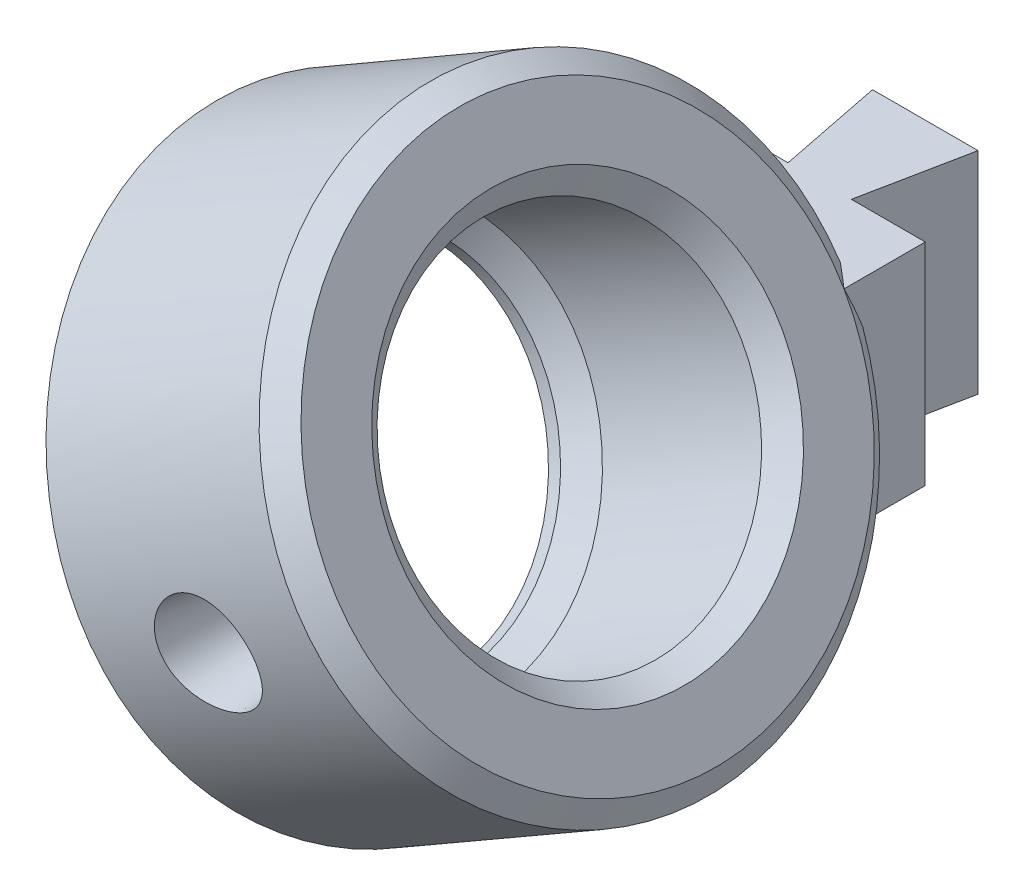
SolidWorks part; units mm, degrees
ref_plane "Front Plane" through (0, 0, 0) normal (0, 0, 1) x (1, 0, 0)
ref_plane "Top Plane" through (0, 0, 0) normal (0, 1, 0) x (1, 0, 0)
ref_plane "Right Plane" through (0, 0, 0) normal (1, 0, 0) x (0, 0, -1)
sketch "Sketch1" plane through (0, 0, 0) normal (0, 1, 0) x (1, 0, 0)
  line L0 (-3.5, 0) -> (-2.5, 5)
  line L1 (-2.5, 5) -> (-7.5, 5)
  line L2 (-7.5, 5) -> (-6.5, 0)
  line L3 (-6.5, 0) -> (-10, 0)
  line L4 (-10, 0) -> (-10, -2.85)
  line L5 (-10, -2.85) -> (0, -2.85)
  line L6 (0, -2.85) -> (0, 0)
  line L7 (0, 0) -> (-3.5, 0)
  line L8 (-5, 5) -> (-5, -2.85)
  dimension "D1" = 5
  dimension "D2" = 5
  dimension "D3" = 3
  dimension "D4" = 1.5
  dimension "D5" = 10
  dimension "D6" = 2.85
extrude "Boss-Extrude1" add sketch "Sketch1" along normal blind 10 contours L8 L1 L2 L3 L4 L5 | L1 L8 L5 L6 L7 L0 region at (-1.75, 0, 0.0931) region at (-5.0931, 0, -1.075)
sketch3d "3DSketch1" plane through (0, 0, 0) normal (0, 0, 1) x (1, 0, 0)
  dimension "D1" = 120
sketch "Sketch2" plane through (4.3301, 2.5, 0) normal (-0.866, -0.5, 0) x (0, 0, -1)
  line L6 (-2.85, -13.6603) -> (-2.85, -5) construction
  line L7 (-2.85, -8.6603) -> (0, -8.6603) construction
  circle A0 centre (-16, -8.6603) radius 13.15
  circle A1 centre (-16, -8.6603) radius 8.15
  dimension "D1" = 16.3
  dimension "D2" = 5
extrude "Boss-Extrude2" add sketch "Sketch2" along normal up to vertex (13.6603 mm away) separate body up to point (-10, 0, 2.85)
sketch "Sketch3" plane through (0, 0, 2.85) normal (0, 0, 1) x (1, 0, 0)
  line L4 (-10, 0) -> (0, 0)
  line L5 (0, 0) -> (0, 10)
  line L6 (0, 10) -> (-10, 10)
  line L7 (-10, 10) -> (-10, 0)
  line L8 (-10, 0) -> (0, 0)
  line L9 (0, 0) -> (0, 10)
  line L10 (0, 10) -> (-10, 10)
  line L11 (-10, 10) -> (-10, 0)
  dimension "D1" = 0
extrude "Boss-Extrude4" add sketch "Sketch3" along normal up to surface up to face at (-5.2551, -8.2184, 16)
sketch "Sketch4" plane through (4.3301, 2.5, 0) normal (0.866, 0.5, 0) x (0, 0, -1)
  circle A0 centre (-16, 8.6603) radius 9.15
  circle A1 centre (-16, 8.6603) radius 8.15 construction
  dimension "D1" = 1
extrude "Cut-Extrude1" cut sketch "Sketch4" against normal blind 9 from offset 2 offset against normal yes
chamfer "Chamfer3" distance 1 angle 45 2 edges at (-5.8071, 16.0581, 16) (-13.6013, 11.5581, 16)
chamfer "Chamfer4" distance 1 angle 45 4 edges at (-7.7551, -3.8882, 16) (-5.2551, -8.2184, 16) (4.075, 2.9419, 16) (6.575, -1.3882, 16)
sketch "Sketch5" plane through (0, 0, -5) normal (0, 0, -1) x (-1, 0, 0)
  line L0 (2.5, 10) -> (7.5, 10) construction
  line L1 (2.5, 10) -> (2.5, 0) construction
  circle A0 centre (5, 5) radius 2.5
  dimension "D1" = 5
  dimension "D2" = 5
  dimension "D3" = 2.5
extrude "Cut-Extrude2" cut sketch "Sketch5" along normal blind 9 draft 7 from offset 35 offset against normal yes
equation "\"D4@Sketch1\"=\"D3@Sketch1\"/2"
equation "\"D6@Sketch1\"=16-13.15"
